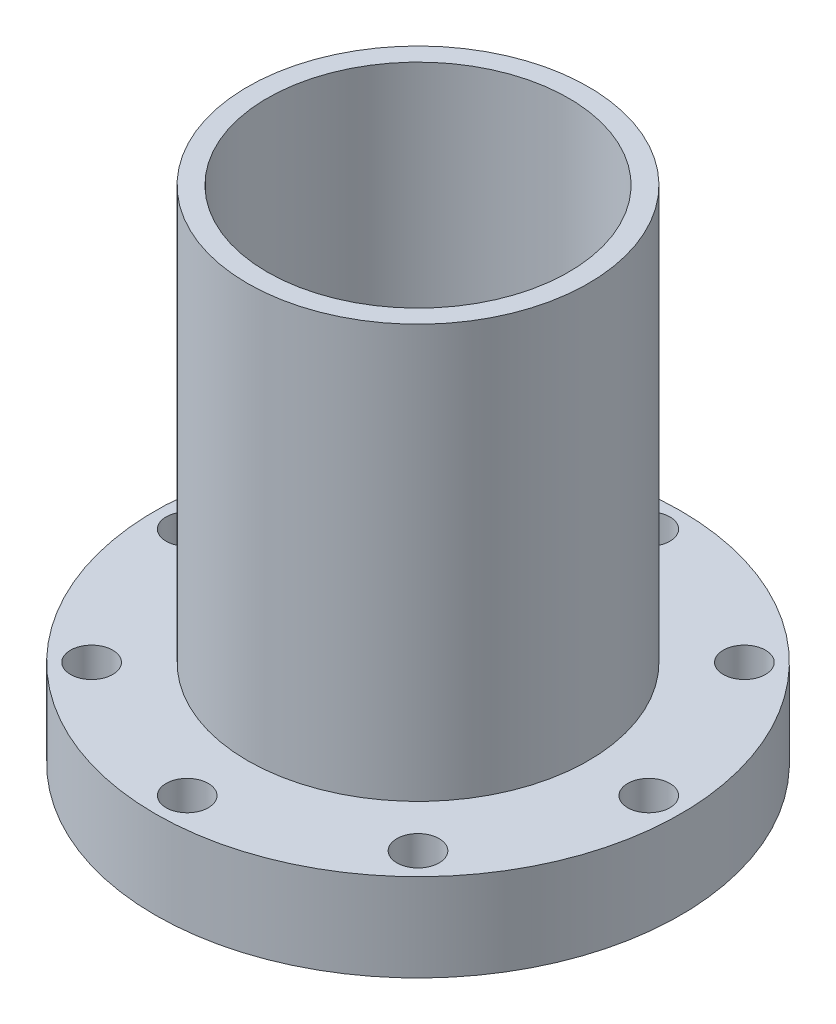
SolidWorks part; units mm, degrees
ref_plane "Front Plane" through (0, 0, 0) normal (0, 0, 1) x (1, 0, 0)
ref_plane "Top Plane" through (0, 0, 0) normal (0, 1, 0) x (1, 0, 0)
ref_plane "Right Plane" through (0, 0, 0) normal (1, 0, 0) x (0, 0, -1)
sketch "Sketch1" plane through (0, 0, 0) normal (0, 1, 0) x (1, 0, 0)
  circle A0 centre (0, 0) radius 34.036
extrude "Extrude1" add sketch "Sketch1" along normal blind 82.55
sketch "Sketch2" plane through (0, 0, 0) normal (0, 1, 0) x (1, 0, 0)
  circle A0 centre (0, 0) radius 52.451
  dimension "D1" = 104.902
extrude "Extrude2" add sketch "Sketch2" against normal blind 17.526
sketch "Sketch3" plane through (0, 0, 0) normal (0, 1, 0) x (1, 0, 0)
  circle A0 centre (0, 0) radius 30.099
  dimension "D1" = 60.198
extrude "Cut-Extrude1" cut sketch "Sketch3" against normal through all and the other way through all
sketch "Sketch4" plane through (0, 0, 0) normal (0, 1, 0) x (1, 0, 0)
  circle A0 centre (0, 46.101) radius 4.2164
  dimension "D1" = 8.4328
extrude "Cut-Extrude2" cut sketch "Sketch4" against normal blind 17.526
ref_axis "Axis1" through (0, 58.677, 0) along (0, -1, 0)
pattern_circular "CirPattern1" count 8 over 360 about axis through (0, 58.677, 0) along (0, -1, 0) of "Cut-Extrude2"
ref_plane "Plane1" through (0, -17.526, 0) normal (0, -1, 0) x (1, 0, 0)
sketch "Sketch9" plane through (0, -17.526, 0) normal (0, -1, 0) x (1, 0, 0)
  line L0 (0, 0) -> (32.5983, 32.5983)
  line L1 (0, 0) -> (13.3652, 32.2665)
  dimension "D1" = 34.925
  dimension "D2" = 22.5
hole_wizard "1/4-20 Tapped Hole2" positions "3DSketch3" profile "Sketch10" tap size "1/4-20" standard "Ansi Inch"
sketch3d "3DSketch3"
  point P0 (13.3652, -17.526, 32.2665)
sketch "Sketch10" plane through (13.3652, -17.526, 32.2665) normal (1, 0, 0) x (0, 0, -1)
  line L0 (0, 0) -> (0, 15.5038)
  line L1 (0, 15.5038) -> (2.5527, 13.97)
  line L2 (2.5527, 13.97) -> (2.5527, 0)
  line L5 (2.5527, 0) -> (0, 0)
  line L10 (0, 15.5038) -> (-2.5527, 13.97) construction
  line L11 (0, -6.35) -> (0, 107.95) construction
  dimension "Tap Drill Dia." = 5.1054
  dimension "Tap Drill Depth" = 13.97
  dimension "Drill Angle" = 118
cosmetic thread "Hole Thread2" parameters "D1"=12.7, "D2"=6.35
pattern_circular "CirPattern3" count 8 over 360 about axis through (0, 58.677, 0) along (0, -1, 0) of "1/4-20 Tapped Hole2"
ref_plane "Plane2" through (0, 82.55, 0) normal (0, 1, 0) x (-1, 0, 0)
sketch "Sketch11" plane through (0, 82.55, 0) normal (0, 1, 0) x (-1, 0, 0)
  point P0 (0, 0)
sketch "Sketch12" plane through (0, 0, 0) normal (0, 0, 1) x (1, 0, 0)
  line L0 (0, 0) -> (0, 91.8051)
